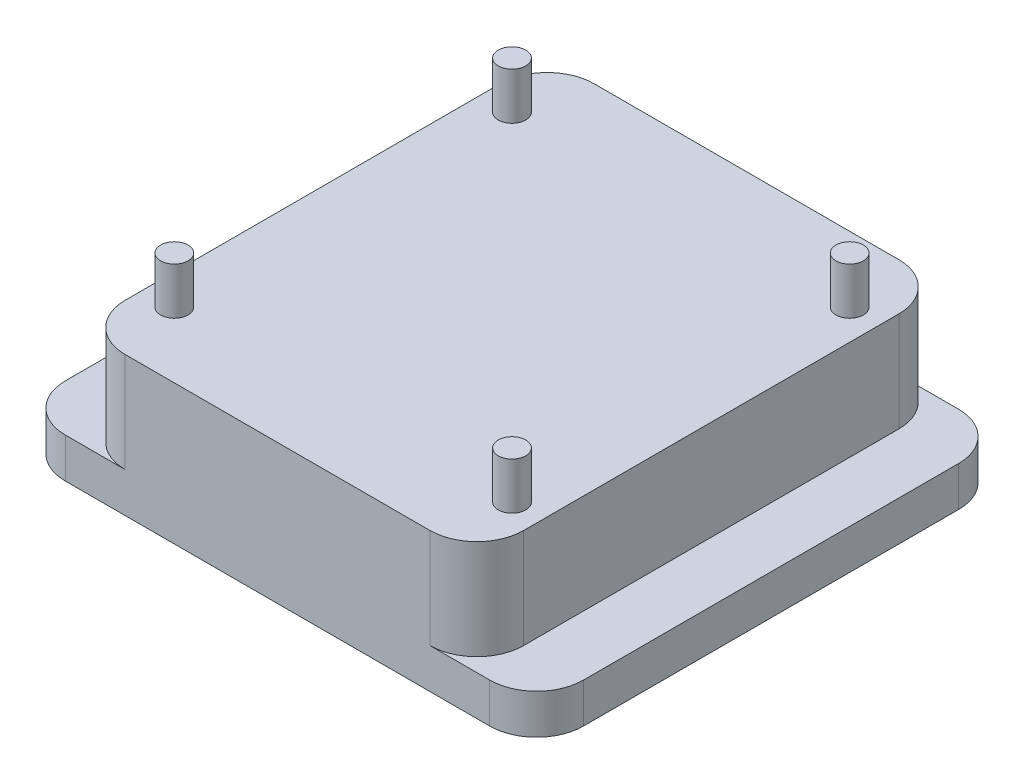
SolidWorks part; units mm, degrees
ref_plane "Front Plane" through (0, 0, 0) normal (0, 0, 1) x (1, 0, 0)
ref_plane "Top Plane" through (0, 0, 0) normal (0, 1, 0) x (1, 0, 0)
ref_plane "Right Plane" through (0, 0, 0) normal (1, 0, 0) x (0, 0, -1)
sketch "Sketch1" plane through (0, 0, 0) normal (0, 0, 1) x (1, 0, 0)
  line L1 (-28.067, -2.159) -> (28.067, -2.159)
  line L2 (-28.067, -2.159) -> (-28.067, 2.159)
  line L3 (-28.067, 2.159) -> (28.067, 2.159)
  line L4 (28.067, -2.159) -> (28.067, 2.159)
  line L5 (-28.067, -2.159) -> (28.067, 2.159) construction
  line L6 (-28.067, 2.159) -> (28.067, -2.159) construction
  line L7 (-21.59, 2.159) -> (21.59, 2.159)
  line L8 (-21.59, 2.159) -> (-21.59, 5.334)
  line L9 (-21.59, 5.334) -> (21.59, 5.334)
  line L10 (21.59, 2.159) -> (21.59, 5.334)
  line L11 (-21.59, 5.334) -> (21.59, 5.334)
  line L12 (-21.59, 5.334) -> (-21.59, 12.954)
  line L13 (-21.59, 12.954) -> (21.59, 12.954)
  line L14 (21.59, 5.334) -> (21.59, 12.954)
  point P0 (0, 0)
  point P10 (0, 5.334)
  point P11 (0, 12.954)
  point P12 (0, 0)
  point P17 (0, 0)
  dimension "D1" = 56.134
  dimension "D2" = 4.318
  dimension "D3" = 43.18
  dimension "D4" = 3.175
  dimension "D5" = 43.18
  dimension "D6" = 7.62
extrude "Boss-Extrude1" add sketch "Sketch1" along normal blind 50.8 contours L11 L14 L13 L12 L9 | L3 L10 L9 L8 | L1 L4 L3 L2 region at (0, 0, 0) region at (0, 3.7465, 0) region at (0, 9.144, 0)
sketch "Sketch2" plane through (0, 12.954, 0) normal (0, 1, 0) x (1, 0, 0)
  line L0 (-21.59, -50.8) -> (-21.59, 0) construction
  line L1 (-18.288, -7.112) -> (18.288, -7.112) construction
  line L2 (-18.288, -7.112) -> (-18.288, -43.688) construction
  line L3 (-18.288, -43.688) -> (18.288, -43.688) construction
  line L4 (18.288, -7.112) -> (18.288, -43.688) construction
  line L5 (-21.59, 0) -> (21.59, 0) construction
  circle A0 centre (-18.288, -7.112) radius 1.4859
  circle A1 centre (18.288, -7.112) radius 1.4859
  circle A2 centre (18.288, -43.688) radius 1.4859
  circle A3 centre (-18.288, -43.688) radius 1.4859
  point P4 (-18.288, -25.4)
  point P5 (-21.59, -25.4)
  point P6 (0, 0)
  point P10 (0, -7.112)
  dimension "D3" = 2.9718
  dimension "D4" = 2.9718
  dimension "D5" = 2.9718
  dimension "D6" = 2.9718
  dimension "D1" = 36.576
  dimension "D2" = 36.576
extrude "Boss-Extrude2" add sketch "Sketch2" along normal blind 5.08
fillet "Fillet1" radius 5.08 4 edges at (-21.59, 7.5565, 0) (21.59, 7.5565, 0) (21.59, 7.5565, 50.8) (-21.59, 7.5565, 50.8)
fillet "Fillet2" radius 5.08 4 edges at (-28.067, 0, 50.8) (-28.067, 0, 0) (28.067, 0, 50.8) (28.067, 0, 0)
